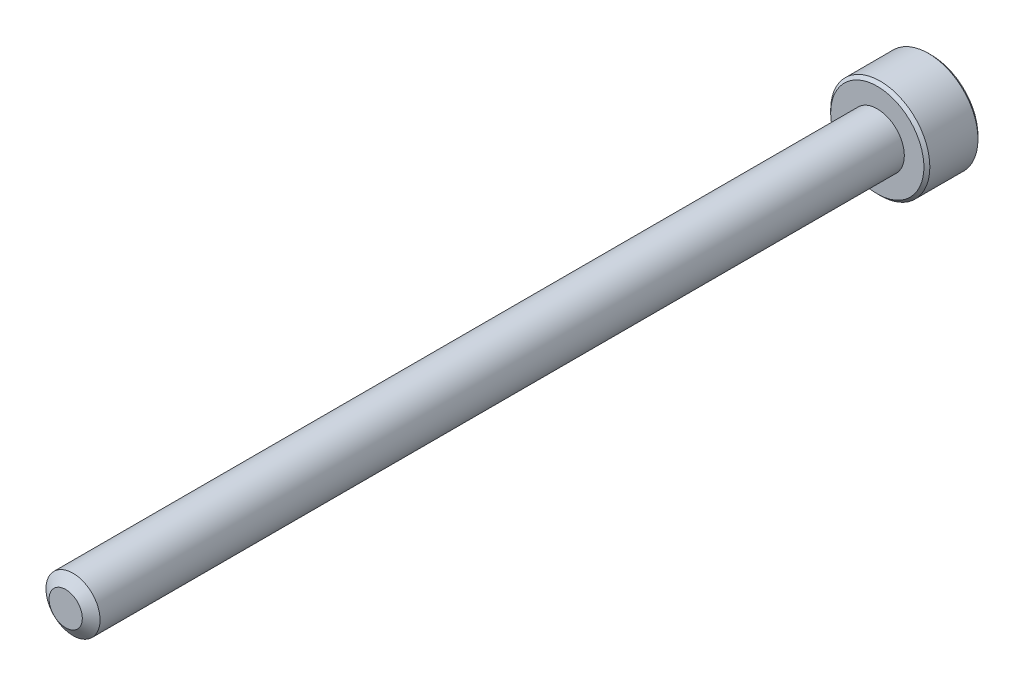
SolidWorks part; units mm, degrees
material "Alloy Steel"
ref_plane "Front Plane" through (0, 0, 0) normal (0, 0, 1) x (1, 0, 0)
ref_plane "Top Plane" through (0, 0, 0) normal (0, 1, 0) x (1, 0, 0)
ref_plane "Right Plane" through (0, 0, 0) normal (1, 0, 0) x (0, 0, -1)
sketch "Sketch1" plane through (0, 0, 0) normal (0, 0, 1) x (1, 0, 0)
  circle A0 centre (0, 0) radius 1.5
  dimension "OD" = 3
extrude "Extrude1" add sketch "Sketch1" against normal blind 45
sketch "Sketch2" plane through (0, 0, 0) normal (0, 0, 1) x (1, 0, 0)
  circle A0 centre (0, 0) radius 1.5 construction
  circle A1 centre (0, 0) radius 1.5
curve "Helix/Spiral1" pitch 0.5 height 45.5 turns 91 parameters "pitch"=0.5
sketch "Sketch3" plane through (0, 0, 0) normal (1, 0, 0) x (0, 0, -1)
  line L0 (-0.4375, 1.5) -> (-0.25, 1.1752)
  line L1 (-0.25, 1.1752) -> (-0.1875, 1.1752)
  line L2 (-0.1875, 1.1752) -> (0, 1.5)
  line L3 (-0.4375, 1.5) -> (0, 1.5)
  line L4 (-0.2187, 1.5) -> (-0.2187, 1.1752) construction
  line L5 (-0.3437, 1.3376) -> (-0.0937, 1.3376) construction
  line L6 (0, 1.5) -> (0, -1.5) construction
  line L7 (0, -1.5) -> (45, -1.5) construction
  point P11 (2.25, -1.5)
  dimension "D1" = 0.0625
  dimension "D2" = 0.25
  dimension "D3" = 60
  dimension "D4" = 2.25
sweep "Cut-Sweep1" [suppressed] cut profiles "Sketch3" path "Helix/Spiral1"
sketch "Sketch4" plane through (0, 0, 0) normal (1, 0, 0) x (0, 0, -1)
  line L0 (0.4053, 1.5) -> (0, 0.9212)
  line L1 (0, 0.9212) -> (0, 1.5)
  line L2 (0.4053, 1.5) -> (0, 1.5)
  line L3 (-0.4375, 1.5) -> (0, 1.5) construction
  line L4 (0, 0) -> (7.0209, 0) construction
  dimension "D1" = 55
  dimension "D2" = 0.254
revolve "Cut-Revolve1" cut sketch "Sketch4" angle 360 about L4
sketch "Sketch5" [suppressed] plane through (0, 0, 0) normal (1, 0, 0) x (0, 0, -1)
  line L0 (45, -1.1822) -> (45, 1.0703) construction
  line L1 (45, 1.5) -> (18.1202, 1.5)
  line L2 (45, 1.5) -> (45, 0)
  line L3 (45, 0) -> (18, 0)
  line L4 (18, 1.1698) -> (18, 0)
  line L5 (18.1202, 1.5) -> (18, 1.1698)
  line L6 (0, 0) -> (9.9695, 0) construction
  point P3 (18, 1.5)
  point P10 (18, 1.5)
  dimension "D1" = 0.3302
  dimension "Thread min" = 18
  dimension "D3" = 20
revolve "partially thread" [suppressed] add sketch "Sketch5" angle 360 about L6
sketch "Sketch6" plane through (0, 0, -45) normal (0, 0, -1) x (-1, 0, 0)
  circle A0 centre (0, 0) radius 2.75
  dimension "head dia" = 5.5
extrude "Extrude2" add sketch "Sketch6" along normal blind 3
sketch "Sketch7" plane through (0, 0, -48) normal (0, 0, -1) x (-1, 0, 0)
  line L1 (0, 1.4434) -> (-1.25, 0.7217)
  line L2 (-1.25, 0.7217) -> (-1.25, -0.7217)
  line L3 (-1.25, -0.7217) -> (0, -1.4434)
  line L4 (0, -1.4434) -> (1.25, -0.7217)
  line L5 (1.25, -0.7217) -> (1.25, 0.7217)
  line L6 (1.25, 0.7217) -> (0, 1.4434)
  circle A0 centre (0, 0) radius 1.25 construction
  dimension "hex dia" = 2.5
extrude "Cut-Extrude1" cut sketch "Sketch7" against normal blind 1.875
sketch "Sketch8" plane through (0, 0, -48) normal (0, 0, -1) x (-1, 0, 0)
  circle A0 centre (0, 0) radius 1.4434
extrude "Cut-Extrude2" cut sketch "Sketch8" against normal through all draft 45
chamfer "Chamfer1" distance 0.165 angle 45 2 edges at (-2.75, 0, -48) (-2.75, 0, -45)
sketch "Sketch9" plane through (0, 0, 0) normal (1, 0, 0) x (0, 0, -1)
  line L0 (0, 1.5) -> (0, -1.5) construction
  line L1 (2.75, 1.5) -> (2.75, -1.5) construction
  dimension "D1" = 2.75
sketch "Sketch10" plane through (0, 0, 0) normal (1, 0, 0) x (0, 0, -1)
  line L0 (45, 1.5) -> (45, 0)
  line L1 (45, 1.5) -> (44.875, 1.5)
  line L2 (44.875, 1.5) -> (44.2537, 0)
  line L3 (45, 0) -> (44.2537, 0)
  line L4 (45, 2.585) -> (45, -2.585) construction
  dimension "D1" = 22.5
  dimension "D2" = 0.125
revolve "Revolve1" [suppressed] add sketch "Sketch10" angle 360 about L3
equation "\"D3@Helix/Spiral1\" = \"screw length@Extrude1\"+\"pitch@Helix/Spiral1\""
equation "\"D1@Sketch3\" = \"pitch@Helix/Spiral1\"*.125"
equation "\"D2@Sketch3\" = \"pitch@Helix/Spiral1\"*.5"
equation "\"D1@Cut-Extrude1\" = \"hex dia@Sketch7\"*.75"
equation "\"D1@Chamfer1\" = \"head dia@Sketch6\"*.03"
equation "\"D1@Sketch9\" = \"pitch@Helix/Spiral1\"*5.5"
equation "\"D2@Sketch10\" = \"pitch@Helix/Spiral1\"*.25"
equation "\"D4@Sketch3\" = \"pitch@Helix/Spiral1\"*4.50"
